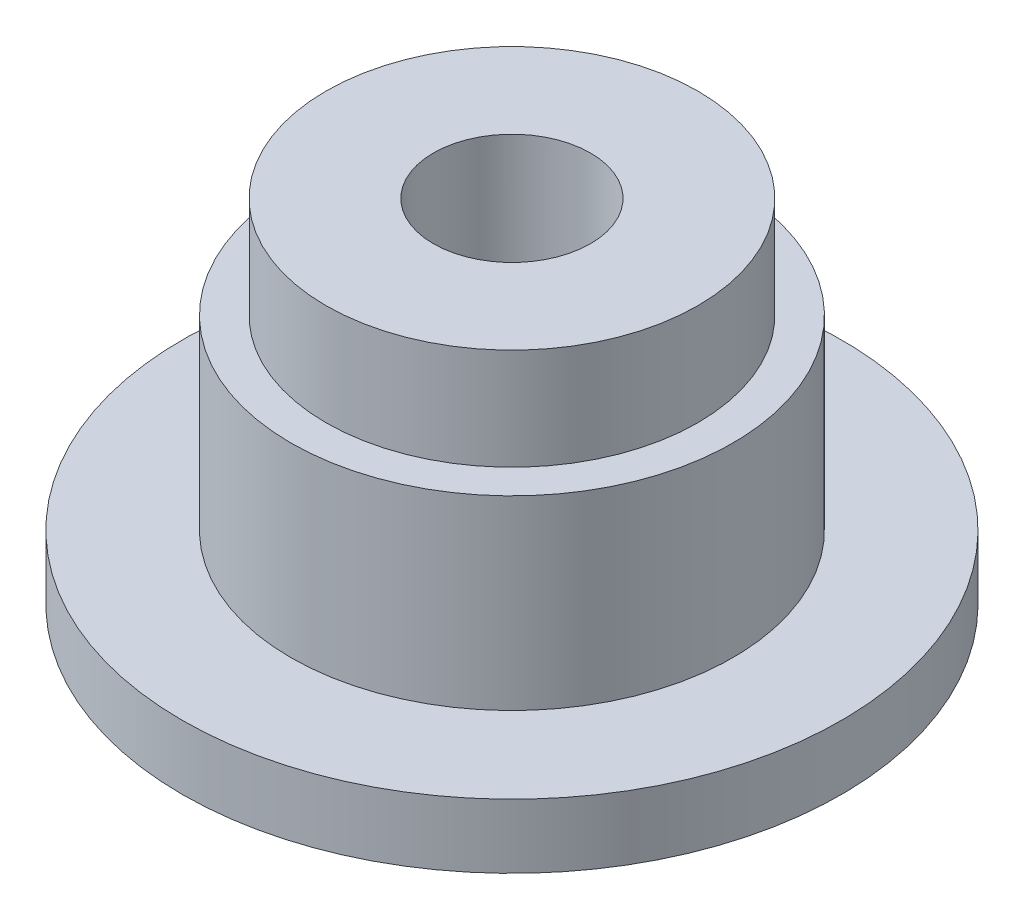
SolidWorks part; units mm, degrees
ref_plane "Front Plane" through (0, 0, 0) normal (0, 0, 1) x (1, 0, 0)
ref_plane "Top Plane" through (0, 0, 0) normal (0, 1, 0) x (1, 0, 0)
ref_plane "Right Plane" through (0, 0, 0) normal (1, 0, 0) x (0, 0, -1)
sketch "Sketch1" plane through (0, 0, 0) normal (0, 1, 0) x (1, 0, 0)
  circle A0 centre (0, 0) radius 11
  circle A1 centre (0, 0) radius 13.075
  circle A2 centre (0, 0) radius 4.65
  dimension "D1" = 22
  dimension "D2" = 26.15
  dimension "D3" = 9.3
extrude "Boss-Extrude1" add sketch "Sketch1" along normal blind 17 contours A0 A2 region at (-10.6889, 0, 0)
extrude "Boss-Extrude2" add sketch "Sketch1<5>" along normal blind 11 contours A1 A0 region at (-12.7052, 0, 0)
sketch "Sketch1<5>" plane through (0, 0, 0) normal (0, 1, 0) x (1, 0, 0) same geometry as "Sketch1"
sketch "Sketch2" plane through (0, 0, 0) normal (0, -1, 0) x (1, 0, 0)
  circle A0 centre (0, 0) radius 19.5
  circle A1 centre (0, 0) radius 4.65
  dimension "D1" = 39
extrude "Boss-Extrude3" add sketch "Sketch2" along normal blind 3.8
